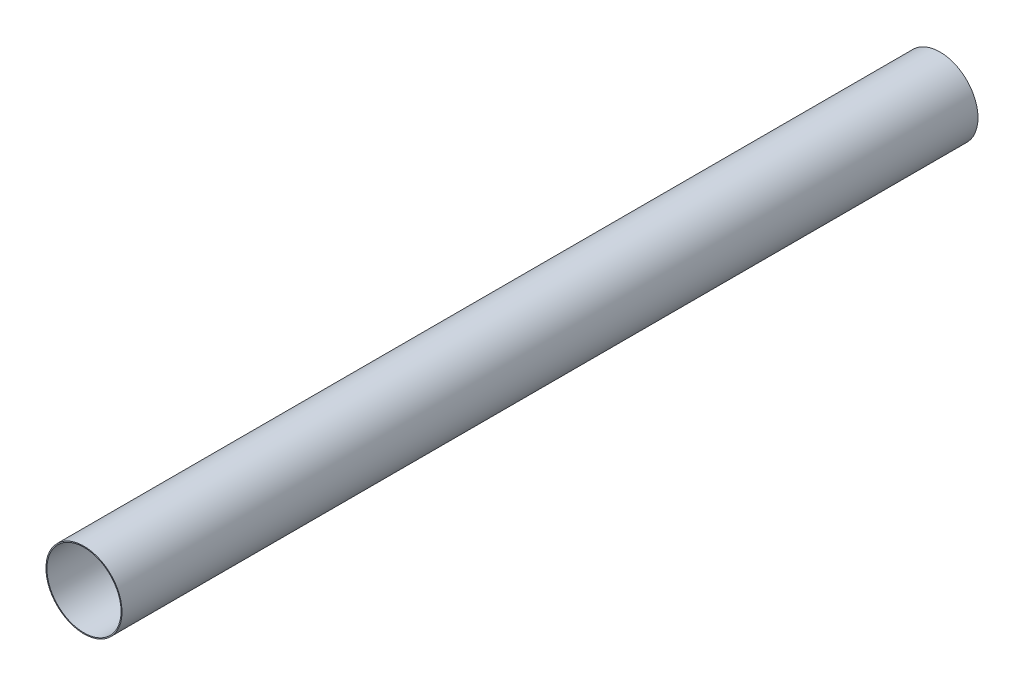
SolidWorks part; units mm, degrees
material "E-Glass Fiber"
ref_plane "Front" through (0, 0, 0) normal (0, 0, 1) x (1, 0, 0)
ref_plane "Top" through (0, 0, 0) normal (0, 1, 0) x (1, 0, 0)
ref_plane "Right" through (0, 0, 0) normal (1, 0, 0) x (0, 0, -1)
sketch "Sketch1" plane through (0, 0, 0) normal (0, 0, 1) x (1, 0, 0)
  circle A0 centre (0, 0) radius 78.2
  circle A1 centre (0, 0) radius 76.2
  dimension "D1" = 156.4
  dimension "D2" = 152.4
extrude "Boss-Extrude1" add sketch "Sketch1" along normal blind 1760
